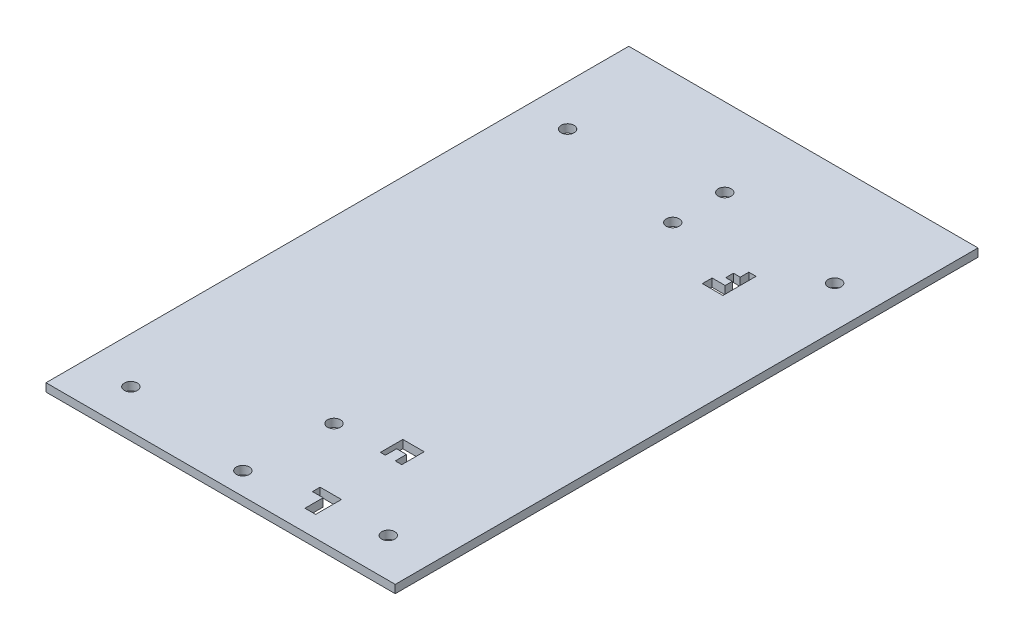
SolidWorks part; units mm, degrees
ref_plane "Front Plane" through (0, 0, 0) normal (0, 0, 1) x (1, 0, 0)
ref_plane "Top Plane" through (0, 0, 0) normal (0, 1, 0) x (1, 0, 0)
ref_plane "Right Plane" through (0, 0, 0) normal (1, 0, 0) x (0, 0, -1)
sketch "Sketch1" plane through (0, 0, 0) normal (0, 1, 0) x (1, 0, 0)
  line L0 (-100.6381, -96.0685) -> (100.6381, -96.0685) construction
  line L5 (100.6381, -96.0685) -> (0, 226.9665) construction
  line L6 (0, 226.9665) -> (-100.6381, -96.0685) construction
  line L7 (-100.6381, -96.0685) -> (0, 267.6095) construction
  line L8 (0, 267.6095) -> (100.6381, -96.0685) construction
  line L9 (-104.394, 249.1485) -> (3.6663, -41.5695) construction
  line L10 (-136.525, 329.0967) -> (136.525, 329.0967)
  line L11 (-136.525, 329.0967) -> (-136.525, -126.5158)
  line L12 (-136.525, -126.5158) -> (136.525, -126.5158)
  line L13 (136.525, 329.0967) -> (136.525, -126.5158)
  line L14 (3.6663, -41.5695) -> (104.394, 249.1485) construction
  line L15 (104.394, 249.1485) -> (-104.394, 249.1485) construction
  line L16 (-104.394, 249.1485) -> (0, -109.1377) construction
  line L17 (0, -109.1377) -> (104.394, 249.1485) construction
  line L18 (69.0129, 197.1736) -> (52.9485, 197.1736)
  line L19 (52.9485, 197.1736) -> (52.9485, 204.7982)
  line L20 (52.9485, 204.7982) -> (63.1353, 204.7982)
  line L21 (63.1353, 204.7982) -> (63.1353, 210.3547)
  line L22 (63.1353, 210.3547) -> (58.0419, 210.3547)
  line L24 (63.3668, 216.3742) -> (63.3668, 223.0882)
  line L25 (63.3668, 223.0882) -> (69.0129, 223.0882)
  line L26 (69.0129, 223.0882) -> (69.0129, 197.1736)
  line L27 (63.3668, 216.3742) -> (58.0419, 216.3742)
  line L28 (58.0419, 216.3742) -> (58.0419, 210.3547)
  line L29 (41.3457, -42.9514) -> (41.3457, -25.4104)
  line L30 (41.3457, -25.4104) -> (58.0419, -25.4104)
  line L31 (58.0419, -25.4104) -> (58.0419, -42.9514)
  line L32 (58.0419, -42.9514) -> (52.9485, -42.9514)
  line L33 (52.9485, -42.9514) -> (52.9485, -34.1809)
  line L34 (52.9485, -34.1809) -> (45.2394, -34.1809)
  line L35 (45.2394, -34.1809) -> (45.2394, -42.9514)
  line L36 (41.3457, -42.9514) -> (45.2394, -42.9514)
  line L37 (58.0419, -110.2615) -> (58.0419, -90.0939)
  line L38 (58.0419, -90.0939) -> (41.3457, -90.0939)
  line L39 (41.3457, -90.0939) -> (41.3457, -96.0685)
  line L40 (41.3457, -96.0685) -> (49.6938, -96.0685)
  line L41 (49.6938, -96.0685) -> (49.6938, -110.2615)
  line L42 (49.6938, -110.2615) -> (58.0419, -110.2615)
  line L43 (0, -96.0685) -> (0, 226.9665) construction
  circle A0 centre (-100.6381, -96.0685) radius 5.08
  circle A1 centre (100.6381, -96.0685) radius 5.08
  circle A2 centre (0, 226.9665) radius 5.08
  circle A3 centre (0, 267.6095) radius 5.08
  circle A4 centre (-104.394, 249.1485) radius 5.08
  circle A5 centre (104.394, 249.1485) radius 5.08
  circle A6 centre (3.6663, -41.5695) radius 5.08
  circle A7 centre (0, -109.1377) radius 5.08
  point P6 (0, 329.0967)
  point P13 (0, -96.0685)
  point P20 (0, 249.1485)
  dimension "D1" = 10.16
  dimension "D2" = 10.16
  dimension "D3" = 10.16
  dimension "D9" = 10.16
  dimension "D10" = 310.1516
  dimension "D15" = 273.05
  dimension "D4" = 338.3483
  dimension "D5" = 338.3483
  dimension "D6" = 100.6381
  dimension "D7" = 377.3455
  dimension "D8" = 377.3455
  dimension "D11" = 307.6736
  dimension "D12" = 104.394
  dimension "D13" = 373.1852
  dimension "D14" = 373.1852
  dimension "D16" = 455.6125
extrude "Boss-Extrude1" add sketch "Sketch1" along normal blind 6.35
